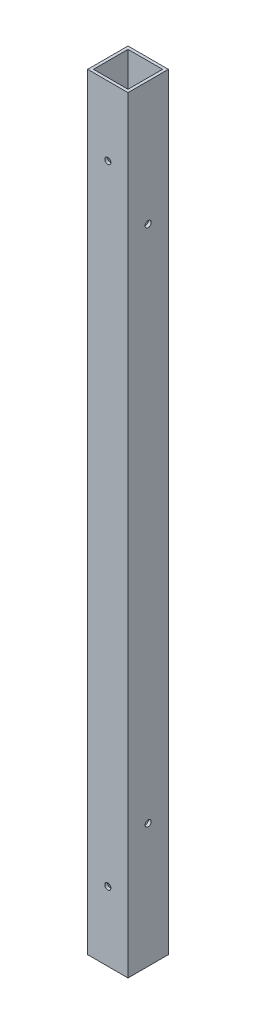
SolidWorks part; units mm, degrees
ref_plane "Front Plane" through (0, 0, 0) normal (0, 0, 1) x (1, 0, 0)
ref_plane "Top Plane" through (0, 0, 0) normal (0, 1, 0) x (1, 0, 0)
ref_plane "Right Plane" through (0, 0, 0) normal (1, 0, 0) x (0, 0, -1)
sketch "Sketch1" plane through (0, 0, 0) normal (0, 1, 0) x (1, 0, 0)
  line L1 (-22.225, -22.225) -> (22.225, -22.225)
  line L2 (-22.225, -22.225) -> (-22.225, 22.225)
  line L3 (-22.225, 22.225) -> (22.225, 22.225)
  line L4 (22.225, -22.225) -> (22.225, 22.225)
  line L5 (-22.225, -22.225) -> (22.225, 22.225) construction
  line L6 (-22.225, 22.225) -> (22.225, -22.225) construction
  line L7 (-19.05, -19.05) -> (19.05, -19.05)
  line L8 (-19.05, -19.05) -> (-19.05, 19.05)
  line L9 (-19.05, 19.05) -> (19.05, 19.05)
  line L10 (19.05, -19.05) -> (19.05, 19.05)
  line L11 (-19.05, -19.05) -> (19.05, 19.05) construction
  line L12 (-19.05, 19.05) -> (19.05, -19.05) construction
  point P0 (0, 0)
  point P6 (0, 0)
  dimension "D1" = 44.45
  dimension "D2" = 3.175
extrude "Boss-Extrude1" add sketch "Sketch1" along normal blind 844.55
sketch "Sketch2" plane through (0, 0, 22.225) normal (0, 0, 1) x (1, 0, 0)
  line L0 (-22.225, 844.55) -> (-22.225, 0) construction
  line L1 (-22.225, 844.55) -> (22.225, 844.55) construction
  line L2 (-22.225, 0) -> (22.225, 0) construction
  point P0 (0, 768.35)
  point P1 (0, 76.2)
  dimension "D1" = 22.225
  dimension "D2" = 76.2
  dimension "D3" = 76.2
hole_wizard "17/64 (0.26563) Diameter Hole1" positions "Sketch3" profile "Sketch4" hole size "17/64" standard "ANSI Inch" end condition through all
sketch "Sketch3" plane through (0, 0, 22.225) normal (0, 0, 1) x (1, 0, 0)
  point P0 (0, 768.35)
  point P3 (0, 76.2)
sketch "Sketch4" plane through (0, 768.35, 22.225) normal (1, 0, 0) x (0, -1, 0)
  line L0 (0, 0) -> (0, 44.45)
  line L1 (0, 44.45) -> (3.3735, 44.45)
  line L2 (3.3735, 44.45) -> (3.3735, 0)
  line L5 (3.3735, 0) -> (0, 0)
  line L11 (0, -6.35) -> (0, 107.95) construction
  dimension "Thru Hole Dia." = 6.747
  dimension "Thru Hole Depth" = 44.45
sketch "Sketch6" plane through (22.225, 0, 0) normal (1, 0, 0) x (0, 0, -1)
  line L0 (22.225, 844.55) -> (22.225, 0) construction
  line L1 (21.4543, 114.3) -> (-28.1773, 114.3) construction
  line L2 (0, 708.025) -> (0, 136.525) construction
  circle A0 centre (0, 136.525) radius 3.3734
  circle A1 centre (0, 708.025) radius 3.3734
  point P8 (22.225, 422.275)
  point P9 (0, 422.275)
  dimension "D1" = 6.7469
  dimension "D2" = 22.225
  dimension "D3" = 22.225
extrude "Cut-Extrude1" cut sketch "Sketch6" against normal through all
